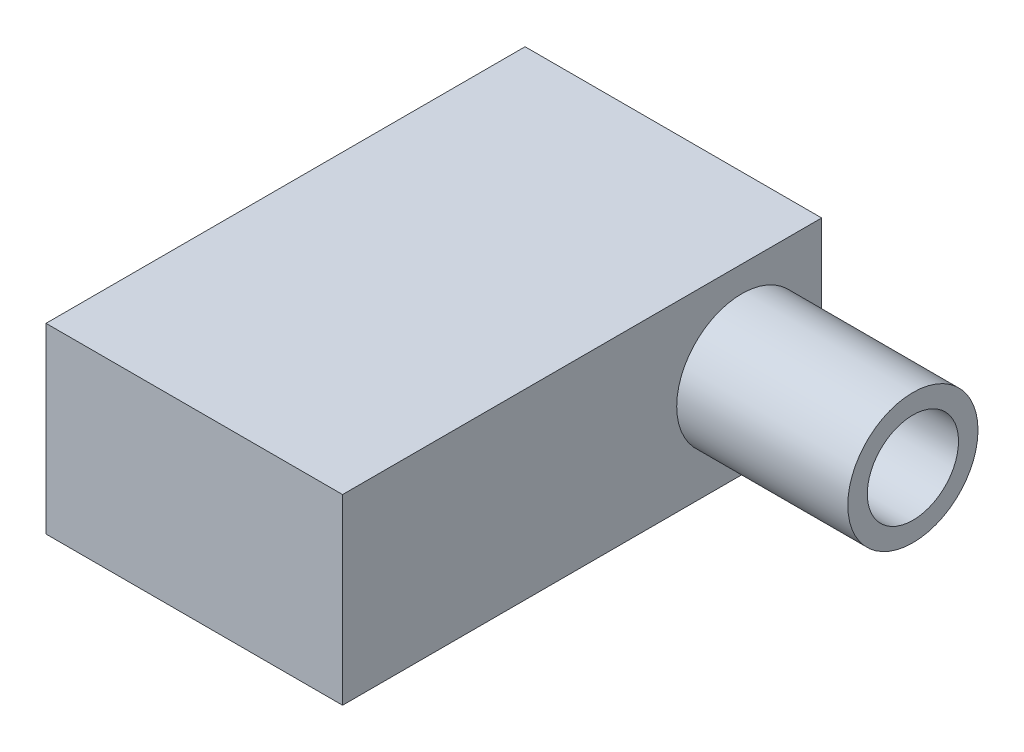
SolidWorks part; units mm, degrees
ref_plane "Front Plane" through (0, 0, 0) normal (0, 0, 1) x (1, 0, 0)
ref_plane "Top Plane" through (0, 0, 0) normal (0, 1, 0) x (1, 0, 0)
ref_plane "Right Plane" through (0, 0, 0) normal (1, 0, 0) x (0, 0, -1)
sketch "Sketch1" plane through (0, 0, 0) normal (0, 0, 1) x (1, 0, 0)
  line L1 (0, 0) -> (130, 0)
  line L2 (0, 0) -> (0, -80)
  line L3 (0, -80) -> (130, -80)
  line L4 (130, 0) -> (130, -80)
  line L5 (10, -10) -> (120, -10)
  line L6 (10, -10) -> (10, -70)
  line L7 (10, -70) -> (120, -70)
  line L8 (120, -10) -> (120, -70)
  dimension "D1" = 10
  dimension "D2" = 10
  dimension "D3" = 80
  dimension "D4" = 10
  dimension "D5" = 10
  dimension "D6" = 80
  dimension "D7" = 130
  dimension "D8" = 110
  dimension "D9" = 60
extrude "Boss-Extrude2" add sketch "Sketch1" along normal blind 200
sketch "Sketch4" plane through (0, 0, 200) normal (0, 0, 1) x (1, 0, 0)
  line L1 (0, 0) -> (130, 0)
  line L2 (0, 0) -> (0, -80)
  line L3 (0, -80) -> (130, -80)
  line L4 (130, 0) -> (130, -80)
extrude "Boss-Extrude3" add sketch "Sketch4" along normal blind 10
sketch "Sketch6" plane through (130, 0, 0) normal (1, 0, 0) x (0, 0, -1)
  circle A0 centre (-35.0025, -39.7809) radius 19.9896
  circle A1 centre (-35.0025, -39.7809) radius 28.5357
extrude "Boss-Extrude5" add sketch "Sketch6" along normal blind 75
extrude "Cut-Extrude1" cut sketch "Sketch6<3>" against normal blind 75 contours A0
sketch "Sketch6<3>" plane through (130, 0, 0) normal (1, 0, 0) x (0, 0, -1) same geometry as "Sketch6"
